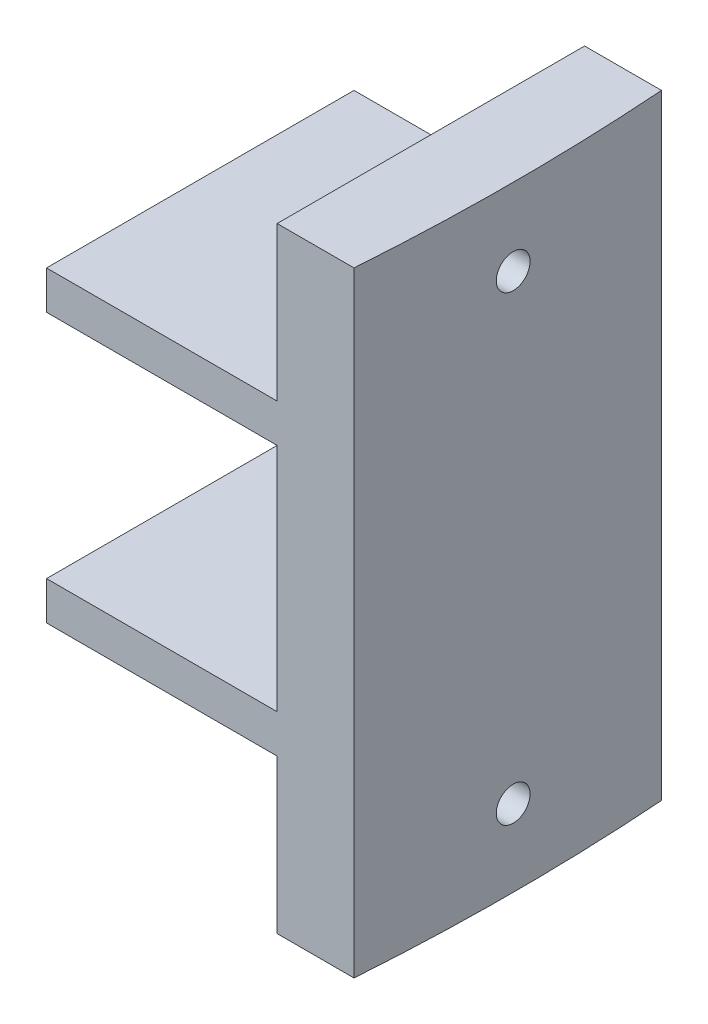
SolidWorks part; units mm, degrees
ref_plane "Front Plane" through (0, 0, 0) normal (0, 0, 1) x (1, 0, 0)
ref_plane "Top Plane" through (0, 0, 0) normal (0, 1, 0) x (1, 0, 0)
ref_plane "Right Plane" through (0, 0, 0) normal (1, 0, 0) x (0, 0, -1)
sketch "Sketch1" plane through (0, 0, 0) normal (0, 1, 0) x (1, 0, 0)
  line L0 (75.9729, 0) -> (82.3229, 0) construction
  line L1 (75.9729, -6.35) -> (88.6729, -6.35)
  line L3 (75.9729, 6.35) -> (88.6729, 6.35)
  line L7 (88.6729, 6.35) -> (75.9729, 6.35)
  line L8 (88.6729, 6.35) -> (88.6729, 4.6501)
  line L9 (88.6729, -6.35) -> (75.9729, -6.35)
  line L10 (75.9729, 6.35) -> (75.9729, -6.35)
  line L11 (75.9729, 3.7178) -> (88.7779, 4.6578) construction
  line L12 (75.9729, -3.7178) -> (88.778, -4.6552) construction
  arc A0 (88.6729, -6.35) -> (88.6729, 6.35) centre (0, 0) ccw
  circle A1 centre (82.3229, 0) radius 1.1303
  dimension "D1" = 177.8
  dimension "D5" = 2.2606
  dimension "D6" = 82.3229
  dimension "D2" = 12.7
  dimension "D3" = 12.7
  dimension "D4" = 6.35
extrude "Boss-Extrude1" add sketch "Sketch1" along normal blind 12.7 contours L3 L10 L1 L8 A1 region at (76.1541, 0, 0)
sketch "Sketch2" plane through (0, 0, 6.35) normal (0, 0, 1) x (1, 0, 0)
  line L1 (75.9729, 1.5875) -> (85.4979, 1.5875)
  line L3 (75.9729, 11.1125) -> (85.4979, 11.1125)
  line L4 (75.9729, 0) -> (88.6729, 0)
  line L5 (88.6729, 0) -> (88.6729, 12.7)
  line L6 (88.6729, 12.7) -> (75.9729, 12.7)
  line L7 (75.9729, 12.7) -> (75.9729, 0)
  line L11 (75.9729, 11.1125) -> (75.9729, 1.5875)
  line L12 (85.4979, 1.5875) -> (85.4979, 11.1125)
  line L13 (75.9729, 6.35) -> (85.4979, 11.1125) construction
  line L14 (75.9729, 6.35) -> (85.4979, 1.5875) construction
  point P2 (75.9729, 6.35)
  dimension "D2" = 9.525
  dimension "D3" = 9.525
  dimension "D1" = 0
extrude "Cut-Extrude1" cut sketch "Sketch2" against normal through all
sketch "Sketch3" plane through (0, 12.7, 0) normal (0, 1, 0) x (1, 0, 0)
  line L0 (75.9729, -6.35) -> (88.6729, -6.35) construction
  line L1 (88.6729, 6.35) -> (75.9729, 6.35) construction
  line L7 (85.4979, -6.35) -> (88.6729, -6.35)
  line L8 (88.6729, 6.35) -> (85.4979, 6.35)
  line L13 (85.4979, 6.35) -> (85.4979, -6.35)
  arc A0 (88.6729, -6.35) -> (88.6729, 6.35) centre (0, 0) ccw construction
  arc A1 (88.6729, -6.35) -> (88.6729, 6.35) centre (0, 0) ccw
  dimension "D1" = 3.175
extrude "Boss-Extrude2" add sketch "Sketch3" along normal blind 6.35 and the other way blind 19.05
sketch "Sketch5" plane through (85.4979, 0, 0) normal (-1, 0, 0) x (0, 0, 1)
  line L0 (6.35, 0) -> (-6.35, 0) construction
  line L1 (-6.35, 0) -> (-6.35, -6.35) construction
  line L2 (-6.35, -6.35) -> (6.35, -6.35) construction
  line L3 (6.35, -6.35) -> (6.35, 0) construction
  line L4 (-6.35, 19.05) -> (-6.35, 12.7) construction
  line L5 (-6.35, 12.7) -> (6.35, 12.7) construction
  line L6 (6.35, 12.7) -> (6.35, 19.05) construction
  line L7 (6.35, 19.05) -> (-6.35, 19.05) construction
  line L8 (6.35, 0) -> (-6.35, 0) construction
  line L9 (-6.35, 0) -> (-6.35, -6.35) construction
  line L10 (-6.35, -6.35) -> (6.35, -6.35) construction
  line L11 (6.35, -6.35) -> (6.35, 0) construction
  line L12 (-6.35, 19.05) -> (-6.35, 12.7) construction
  line L13 (-6.35, 12.7) -> (6.35, 12.7) construction
  line L14 (6.35, 12.7) -> (6.35, 19.05) construction
  line L15 (6.35, 19.05) -> (-6.35, 19.05) construction
  line L16 (0, 19.05) -> (0, 12.7) construction
  line L17 (0, 0) -> (0, -6.35) construction
  circle A0 centre (0, 15.875) radius 0.6985
  circle A1 centre (0, -3.175) radius 0.6985
  dimension "D1" = 1.397
extrude "Cut-Extrude2" cut sketch "Sketch5" against normal through all
